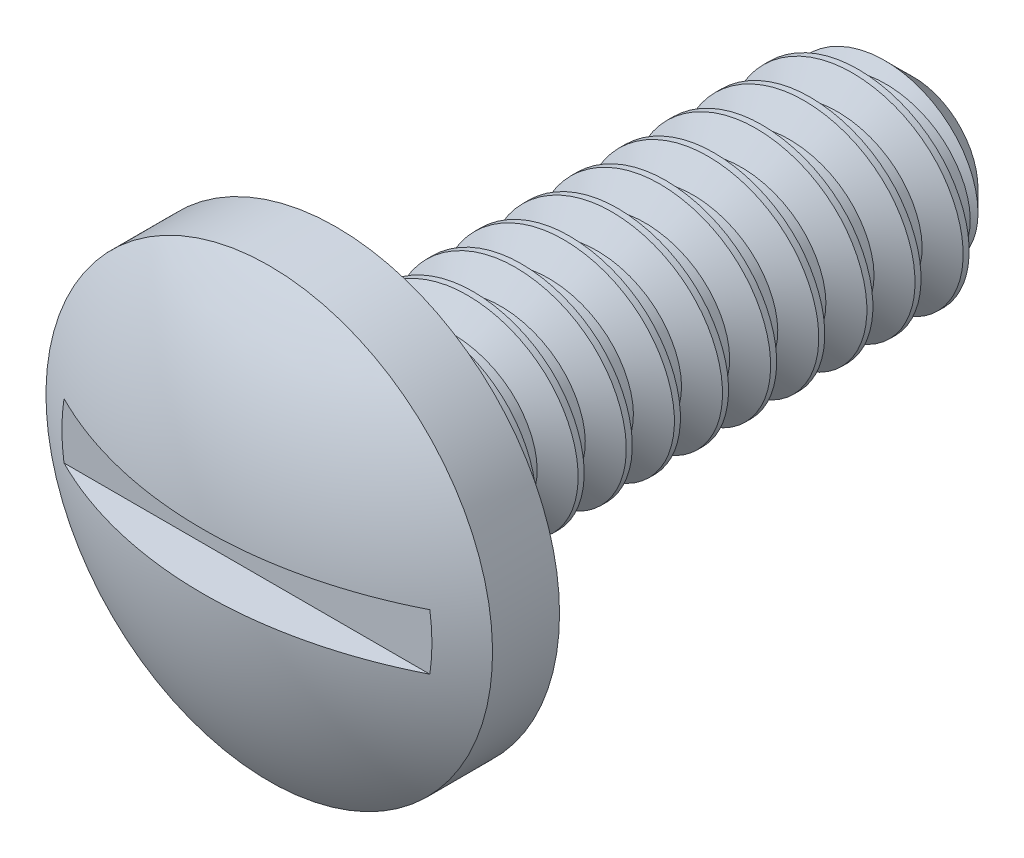
SolidWorks part; units mm, degrees
ref_plane "Front" through (0, 0, 0) normal (0, 0, 1) x (1, 0, 0)
ref_plane "Top" through (0, 0, 0) normal (0, 1, 0) x (1, 0, 0)
ref_plane "Right" through (0, 0, 0) normal (1, 0, 0) x (0, 0, -1)
sketch "Sketch1" plane through (0, 0, 0) normal (0, 0, 1) x (1, 0, 0)
  circle A0 centre (0, 0) radius 3.683
  dimension "Head Dia" = 7.366
extrude "Extrude3" add sketch "Sketch1" along normal blind 2.2098
ref_plane "Plane1" through (0, 0, 2.2098) normal (0, 0, 1) x (1, 0, 0)
sketch "Sketch11" plane through (0, 0, 0) normal (1, 0, 0) x (0, 0, -1)
  line L1 (-2.2098, 3.683) -> (-2.2098, -3.683) construction
  line L4 (-1.1049, 3.937) -> (-1.1049, 3.683)
  line L6 (-1.1049, 3.937) -> (-2.4638, 3.937)
  line L7 (-2.4638, 3.937) -> (-2.4638, 0)
  line L8 (-2.4638, 0) -> (-2.2098, 0)
  line L9 (0, 3.683) -> (-2.2098, 3.683) construction
  line L11 (0, 0) -> (-2.2098, 0) construction
  arc A0 (-1.1049, 3.683) -> (-2.2098, 0) centre (4.481, 0) ccw
  dimension "D1" = 0.254
  dimension "D2" = 1.1049
revolve "Cut-Revolve3" cut sketch "Sketch11" angle 360 about L11
sketch "Sketch14" plane through (0, 0, 0) normal (1, 0, 0) x (0, 0, -1)
  line L0 (0.1984, 1.323) -> (0.4465, 1.7526) construction
  line L2 (0.4465, 1.7526) -> (0.5457, 1.7526)
  line L3 (0.5457, 1.7526) -> (0.7937, 1.323) construction
  line L4 (0.7937, 1.323) -> (0.1984, 1.323) construction
  line L5 (0.7937, 1.323) -> (0.9922, 1.323) construction
  line L6 (0.1984, 1.323) -> (0, 1.323) construction
  line L10 (0, 3.683) -> (0, -3.683) construction
  line L11 (0.4465, 1.7526) -> (0.1984, 1.323)
  line L12 (0.1984, 1.323) -> (0.7937, 1.323)
  line L13 (0.7937, 1.323) -> (0.5457, 1.7526)
  line L14 (0, 0) -> (-2.2098, 0) construction
  line L15 (0, 0) -> (-2.2098, 0) construction
  point P11 (0.4961, 1.7526)
  dimension "D1" = 60
  dimension "Pitch" = 0.7937
  dimension "D3" = 0.1984
  dimension "D4" = 0.0992
  dimension "Screw Dia" = 3.5052
ref_plane "Plane2" through (0, 0, -0.4961) normal (0, 0, 1) x (1, 0, 0)
sketch "Sketch15" plane through (0, 0, -0.4961) normal (0, 0, 1) x (1, 0, 0)
  circle A0 centre (0, 0) radius 1.7526
curve "Helix/Spiral1" pitch 0.7937 height 1.1906 radius 1.7526 centre (0, 0, -0.4961) axis (0, 0, -1) start towards (0, 1, 0)
sketch "Sketch18" plane through (0, 0, 0) normal (1, 0, 0) x (0, 0, -1)
  line L1 (0, 0) -> (9.525, 0)
  line L2 (0, 0) -> (0, 1.323)
  line L3 (0, 1.323) -> (9.525, 1.323)
  line L4 (9.525, 0) -> (9.525, 1.323)
  dimension "Body Length" = 9.525
revolve "Revolve1" add sketch "Sketch18" angle 360 about L11
sweep "Sweep1" add profiles "Sketch14" path "Helix/Spiral1"
pattern_linear "LPattern3" count 11 spacing 0.7937 along (0, 0, 1) count 2 spacing 0.7937 along (0, 0, 1) of "Sweep1"
sketch "Sketch13" plane through (0, 0, 0) normal (1, 0, 0) x (0, 0, -1)
  line L0 (9.525, 1.0601) -> (8.8325, 1.7526)
  line L1 (0, 1.323) -> (9.525, 1.323) construction
  line L2 (8.8325, 1.7526) -> (9.525, 1.7526)
  line L3 (9.525, 1.7526) -> (9.525, 1.0601) construction
  line L4 (9.525, 1.0601) -> (12.065, 1.0601)
  line L5 (0, 0) -> (9.525, 0) construction
  line L6 (0.4465, 1.7526) -> (0.5457, 1.7526) construction
  line L7 (12.065, 1.0601) -> (12.065, 1.7526)
  line L8 (12.065, 1.7526) -> (9.525, 1.7526)
  dimension "D1" = 45
  dimension "D2" = 0.2629
  dimension "D3" = 2.54
revolve "Cut-Revolve4" cut sketch "Sketch13" angle 360 about L5
sketch "Sketch12" plane through (0, 0, 2.2098) normal (0, 0, 1) x (1, 0, 0)
  line L0 (-3.683, -0.4604) -> (3.683, 0.4604) construction
  line L1 (-3.683, 0.4604) -> (3.683, 0.4604)
  line L2 (-3.683, 0.4604) -> (-3.683, -0.4604)
  line L3 (-3.683, -0.4604) -> (3.683, -0.4604)
  line L4 (3.683, 0.4604) -> (3.683, -0.4604)
  circle A1 centre (0, 0) radius 3.683 construction
  dimension "D1" = 0.9207
extrude "Cut-Extrude1" cut sketch "Sketch12" against normal blind 0.7366
equation "\"D3@LPattern3\"=\"Pitch@Sketch14\""
equation "\"D1@LPattern3\"=(\"Body Length@Sketch18\"/\"Pitch@Sketch14\")-1"
equation "\"D3@Sketch14\" = \"Pitch@Sketch14\"/4"
equation "\"D4@Sketch14\" = \"Pitch@Sketch14\"/8"
equation "\"D4@LPattern3\" = \"D3@LPattern3\""
equation "\"D4@Helix/Spiral1\" = \"Pitch@Sketch14\""
equation "\"D1@Cut-Extrude1\" = \"Head Ht@Extrude3\"/3"
equation "\"D1@Sketch12\" = \"Head Dia@Sketch1\"/8"
equation "\"D2@Sketch11\" = \"Head Ht@Extrude3\"/2"
equation "\"D2@Sketch13\" = \"Screw Dia@Sketch14\"*.075"
